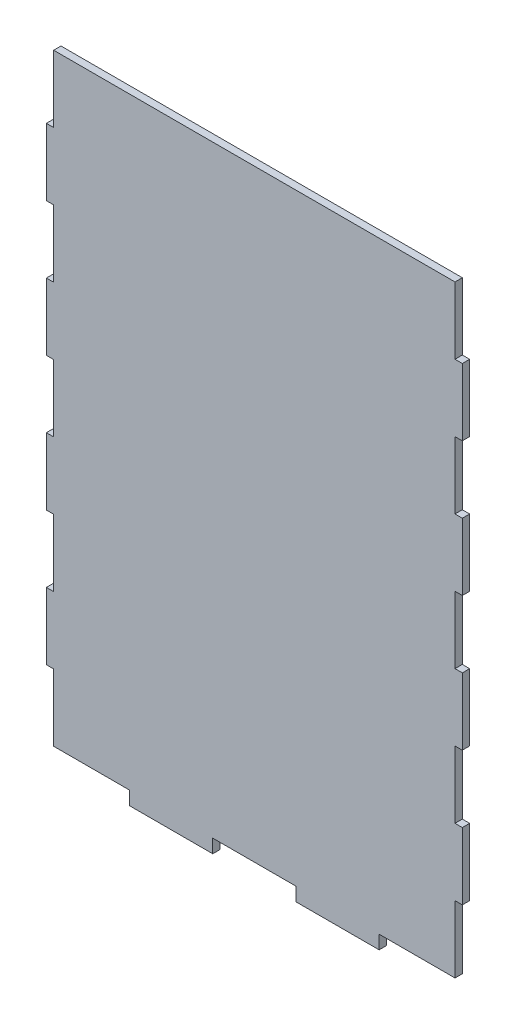
SolidWorks part; units mm, degrees
ref_plane "Ön Düzlem" through (0, 0, 0) normal (0, 0, 1) x (1, 0, 0)
ref_plane "Üst Düzlem" through (0, 0, 0) normal (0, 1, 0) x (1, 0, 0)
ref_plane "Sağ Düzlem" through (0, 0, 0) normal (1, 0, 0) x (0, 0, -1)
sketch "Sketch1" plane through (0, 0, 0) normal (0, 0, 1) x (1, 0, 0)
  line L0 (46.02, -108.65) -> (74, -108.65)
  line L3 (74, 113.65) -> (-74, 113.65)
  line L5 (73.3256, -108.65) -> (-74, 109.6493) construction
  line L6 (74, 109.6493) -> (-73.3256, -108.65) construction
  line L7 (-74, -108.65) -> (-46.02, -108.65)
  line L8 (-15.34, -108.65) -> (15.34, -108.65)
  line L9 (-74, -108.65) -> (-74, -83.95)
  line L11 (74, -108.65) -> (74, -83.95)
  line L13 (-74, -59.25) -> (-74, -34.55)
  line L15 (-74, -9.85) -> (-74, 14.85)
  line L16 (-76.7, 14.85) -> (-76.7, 39.55)
  line L17 (-74, 39.55) -> (-74, 64.25)
  line L18 (-76.7, -34.55) -> (-76.7, -9.85)
  line L19 (-74, 88.95) -> (-74, 113.65)
  line L20 (76.7, -34.55) -> (76.7, -9.85)
  line L21 (74, -59.25) -> (74, -34.55)
  line L22 (76.7, 14.85) -> (76.7, 39.55)
  line L23 (74, -9.85) -> (74, 14.85)
  line L24 (76.7, 64.25) -> (76.7, 88.95)
  line L25 (74, 39.55) -> (74, 64.25)
  line L26 (46.02, -113.65) -> (15.34, -113.65)
  line L27 (74, 88.95) -> (74, 113.65)
  line L28 (-74, 88.95) -> (-76.7, 88.95)
  line L29 (-74, 64.25) -> (-76.7, 64.25)
  line L30 (-74, 39.55) -> (-76.7, 39.55)
  line L31 (-74, 14.85) -> (-76.7, 14.85)
  line L32 (-74, -9.85) -> (-76.7, -9.85)
  line L33 (-74, -34.55) -> (-76.7, -34.55)
  line L34 (-74, -83.95) -> (-76.7, -83.95)
  line L35 (74, -83.95) -> (76.7, -83.95)
  line L36 (74, 88.95) -> (76.7, 88.95)
  line L37 (74, 64.25) -> (76.7, 64.25)
  line L38 (74, 39.55) -> (76.7, 39.55)
  line L39 (74, 14.85) -> (76.7, 14.85)
  line L40 (74, -9.85) -> (76.7, -9.85)
  line L41 (74, -34.55) -> (76.7, -34.55)
  line L42 (74, -59.25) -> (76.7, -59.25)
  line L43 (-76.7, 64.25) -> (-76.7, 88.95)
  line L44 (-76.7, -83.95) -> (-76.7, -61.75)
  line L45 (76.7, -83.95) -> (76.7, -59.25)
  line L46 (-74, -59.25) -> (-76.7, -59.25)
  line L47 (-15.34, -113.65) -> (-46.02, -113.65)
  line L48 (-76.7, -61.75) -> (-76.7, -59.25)
  line L49 (-46.02, -113.65) -> (-46.02, -108.65)
  line L50 (-15.34, -113.65) -> (-15.34, -108.65)
  line L51 (15.34, -113.65) -> (15.34, -108.65)
  line L52 (46.02, -113.65) -> (46.02, -108.65)
  point P0 (0, 0)
  point P42 (0, 0)
extrude "Boss-Extrude2" add sketch "Sketch1" along normal blind 2.7
